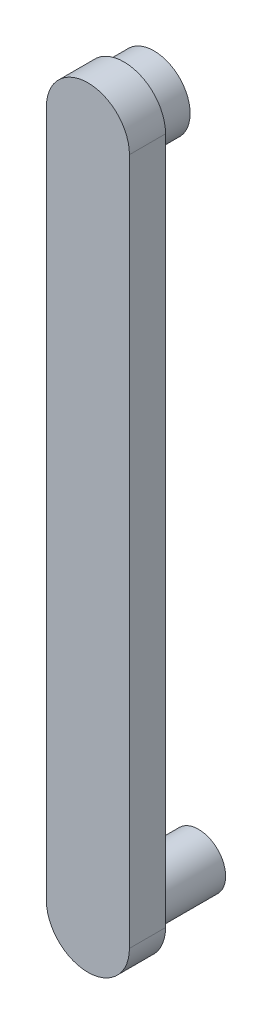
SolidWorks part; units mm, degrees
material "Gray Cast Iron"
ref_plane "Front Plane" through (0, 0, 0) normal (0, 0, 1) x (1, 0, 0)
ref_plane "Top Plane" through (0, 0, 0) normal (0, 1, 0) x (1, 0, 0)
ref_plane "Right Plane" through (0, 0, 0) normal (1, 0, 0) x (0, 0, -1)
sketch "Sketch1" plane through (0, 0, 0) normal (0, 0, 1) x (1, 0, 0)
  line L0 (0, 0) -> (0, 1903.73) construction
  line L1 (-115, 0) -> (-115, 1903.73)
  line L2 (115, 0) -> (115, 1903.73)
  arc A0 (-115, 0) -> (115, 0) centre (0, 0) ccw
  arc A1 (115, 1903.73) -> (-115, 1903.73) centre (0, 1903.73) ccw
  circle A2 centre (0, 1903.73) radius 100
  circle A3 centre (0, 0) radius 75
  point P3 (0, 951.865)
  dimension "D3" = 200
  dimension "D4" = 150
  dimension "D1" = 230
  dimension "D2" = 1903.73
extrude "Boss-Extrude1" add sketch "Sketch1" along normal blind 100 contours A1 L1 A0 L2
extrude "Boss-Extrude3" add sketch "Sketch1<4>" against normal blind 83.1001 contours A2 region at (0, 1903.73, 0)
sketch "Sketch1<4>" plane through (0, 0, 0) normal (0, 0, 1) x (1, 0, 0) same geometry as "Sketch1"
extrude "Boss-Extrude4" add sketch "Sketch1<5>" against normal blind 206.3806 contours A3 region at (0, 0, 0)
sketch "Sketch1<5>" plane through (0, 0, 0) normal (0, 0, 1) x (1, 0, 0) same geometry as "Sketch1"
